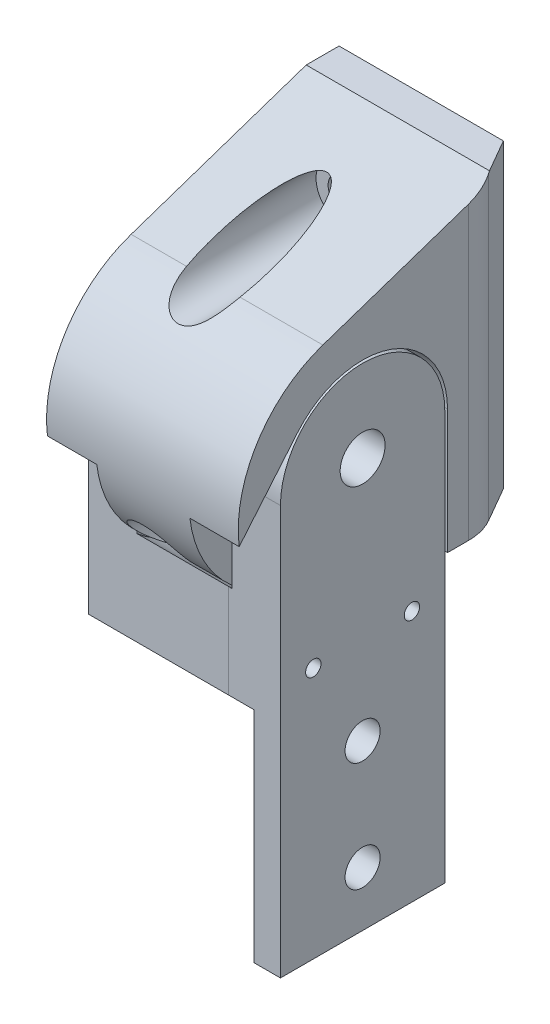
SolidWorks part; units mm, degrees
note: The reader was unsure of these and kept them because the rebuilt part matched: shared geometry of "Sketch1<3>", "Sketch1<5>", "Sketch1<8>", "Sketch1<9>", "Sketch1<11>", "Sketch2<4>", "Sketch2<5>", "Sketch3<3>", "Sketch7<3>", "Sketch7<5>".
ref_plane "Front Plane" through (0, 0, 0) normal (1, 0, 0) x (0, 1, 0)
ref_plane "Top Plane" through (0, 0, 0) normal (0, 0, 1) x (0, 1, 0)
ref_plane "Right Plane" through (0, 0, 0) normal (0, 1, 0) x (-1, 0, 0)
sketch "Sketch1" plane through (0, 0, 0) normal (1, 0, 0) x (0, 1, 0)
  line L0 (-22.7, 0) -> (-22.7, -30.7)
  line L1 (-74.7, 15) -> (-17.5379, 15)
  line L2 (-74.7, 15) -> (-74.7, -15)
  line L3 (-74.7, -15) -> (-17.5379, -15)
  line L4 (-17.5379, 15) -> (-17.5379, -15) construction
  line L5 (-22.7, -30.7) -> (32.3, -30.7)
  line L6 (21.5069, 7.2625) -> (32.3, -24.7)
  line L7 (32.3, -24.7) -> (32.3, -30.7)
  line L8 (-22.7, 0) -> (-17.5379, 0) construction
  line L9 (-74.7, 0) -> (-17.5379, 0) construction
  line L10 (-17.5379, 15) -> (0, 15)
  line L11 (0, -15) -> (-17.5379, -15)
  line L12 (-34.7, 15) -> (-34.7, -15)
  line L13 (-22.7, -15.5) -> (0, -15.5)
  line L14 (9.9632, 11.8737) -> (-2.7411, 22.5339)
  line L15 (-23.0776, 0) -> (-23.0776, -15)
  circle A0 centre (0, 0) radius 4.1
  circle A1 centre (0, 0) radius 7.7
  circle A2 centre (0, 0) radius 22.7
  arc A3 (0, 15) -> (0, -15) centre (0, 0) cw
  arc A4 (-17.5379, -15) -> (-17.5379, 15) centre (0, 0) cw
  circle A5 centre (-44.7, 0) radius 3.2
  circle A7 centre (-64.7, 0) radius 3.2
  arc A8 (0, -15.5) -> (9.9632, 11.8737) centre (0, 0) ccw
  point P5 (-17.0379, 15)
  point P7 (-67.9, 0)
  point P11 (-7.7, 0)
  point P15 (0, -22.7)
  dimension "D1" = 8.2
  dimension "D2" = 15.4
  dimension "D11" = 6.4
  dimension "D3" = 30
  dimension "D4" = 15
  dimension "D5" = 8
  dimension "D6" = 55
  dimension "D7" = 6
  dimension "D8" = 0.5
  dimension "D9" = 12
  dimension "D10" = 10
  dimension "D12" = 10
  dimension "D15" = 0.5
  dimension "D16" = 40
  dimension "D17" = 7.2
  dimension "D13" = 20
  dimension "D14" = 6.8
extrude "Boss-Extrude1" add sketch "Sketch1" along normal mid plane 17 contours L10 A2 L11 A1 | L13 A8 L14 A2 L10 A1 L11 | L3 A4 L0 | A4 L11 A2 L0 | A2 L11 L3 L0 L13
extrude "Boss-Extrude2" add sketch "Sketch1<3>" along normal mid plane 35 contours A2 L13 L0 L5 L7 L6 | A8 L13 A2 L14
sketch "Sketch1<3>" plane through (0, 0, 0) normal (1, 0, 0) x (0, 1, 0) same geometry as "Sketch1"
ref_plane "Plane1" through (8.7, 0, 0) normal (1, 0, 0) x (0, 0, -1)
extrude "Boss-Extrude3" add sketch "Sketch1<5>" along normal up to surface (8.8 mm away) from surface at 8.7 separate body contours A3 L10 A2 L11 A1 | A4 L0 A2 L10 | L3 A4 L0 | A4 L11 A2 L0 | L0 A4 L15 L3 | A1 A0 up to face at (17.5, 7.5284, -9.326) starting at plane "Plane1"
sketch "Sketch1<5>" plane through (0, 0, 0) normal (1, 0, 0) x (0, 1, 0) same geometry as "Sketch1"
ref_plane "Plane2" through (12.7, 0, 0) normal (-1, 0, 0) x (0, 0, 1)
extrude "Boss-Extrude5" add sketch "Sketch1<8>" along direction (1, 0, 0) on the side of the normal up to vertex (17.5 mm away) from surface at 12.7
sketch "Sketch1<8>" plane through (0, 0, 0) normal (1, 0, 0) x (0, 1, 0) same geometry as "Sketch1"
extrude "Boss-Extrude6" add sketch "Sketch1<9>" along normal up to surface (30.2 mm away) from vertex at -17.5 contours L15 A4 L1 L12 L3 up to face at (12.7, -64.7, 3.2) starting at point (-17.5, -22.7, -15.5)
sketch "Sketch1<9>" plane through (0, 0, 0) normal (1, 0, 0) x (0, 1, 0) same geometry as "Sketch1"
ref_plane "Plane3" through (-8.7, 0, 0) normal (-1, 0, 0) x (0, 0, 1)
extrude "Boss-Extrude7" add sketch "Sketch1<11>" against normal up to vertex from surface contours A3 L10 A2 L11 A1 | L3 A4 L0 | A4 L11 A2 L0 | L0 A4 L15 L3 | A4 L0 A2 L10 | A1 A0
sketch "Sketch1<11>" plane through (0, 0, 0) normal (1, 0, 0) x (0, 1, 0) same geometry as "Sketch1"
ref_plane "Plane4" through (8, 0, 0) normal (1, 0, 0) x (0, 1, 0)
split "Split1" trim tools "Plane4" bodies to split 109 resulting bodies 110 111
sketch "Sketch2" plane through (-17.5, 0, 0) normal (-1, 0, 0) x (0, -1, 0)
  line L4 (23.0776, 0) -> (23.0776, -15)
  line L5 (34.7, 15) -> (17.5379, 15)
  line L6 (34.7, -15) -> (34.7, 15)
  line L7 (23.0776, -15) -> (34.7, -15)
  line L8 (23.0776, 0) -> (23.0776, -15)
  line L9 (34.7, 15) -> (17.5379, 15)
  line L10 (34.7, -15) -> (34.7, 15)
  line L11 (23.0776, -15) -> (34.7, -15)
  circle A0 centre (28.7, -9) radius 1.7
  arc A1 (23.0776, 0) -> (17.5379, 15) centre (0, 0) ccw
  arc A2 (23.0776, 0) -> (17.5379, 15) centre (0, 0) ccw
  circle A3 centre (28.7, 9) radius 1.7
  circle A4 centre (28.7, 9) radius 3
  circle A5 centre (28.7, -9) radius 3
  circle A6 centre (28.7, 9) radius 1.4
  circle A7 centre (28.7, -9) radius 1.4
  dimension "D7" = 6
  dimension "D2" = 3.4
  dimension "D3" = 3.4
  dimension "D8" = 6
  dimension "D9" = 2.8
  dimension "D10" = 2.8
  dimension "D4" = 6
  dimension "D5" = 6
extrude "Cut-Extrude1" cut sketch "Sketch2" against normal through all contours A3 | A0 | A6 | A7
extrude "Cut-Extrude2" cut sketch "Sketch2<4>" against normal blind 4 contours A4 A3 | A5 A0
sketch "Sketch2<4>" plane through (-17.5, 0, 0) normal (-1, 0, 0) x (0, -1, 0) same geometry as "Sketch2"
extrude "Cut-Extrude3" cut sketch "Sketch2<5>" against normal through all contours A6 | A7
sketch "Sketch2<5>" plane through (-17.5, 0, 0) normal (-1, 0, 0) x (0, -1, 0) same geometry as "Sketch2"
sketch "Sketch3" plane through (0, -34.7, 0) normal (0, -1, 0) x (1, 0, 0)
  line L0 (-17.5, 0) -> (-2.5, 0) construction
  line L1 (-17.5, 15) -> (-17.5, -15) construction
  circle A0 centre (-2.5, 0) radius 3.2
  circle A1 centre (-2.5, 0) radius 6
  dimension "D1" = 6.4
  dimension "D2" = 12
  dimension "D3" = 15
extrude "Cut-Extrude4" cut sketch "Sketch3" against normal through all
extrude "Cut-Extrude5" cut sketch "Sketch3<3>" against normal through all from offset 5 offset against normal yes
sketch "Sketch3<3>" plane through (0, -34.7, 0) normal (0, -1, 0) x (1, 0, 0) same geometry as "Sketch3"
sketch "Sketch6" plane through (0, 32.3, 0) normal (0, 1, 0) x (-1, 0, 0)
  line L1 (-17.5, -15.5) -> (-17.5, -30.7) construction
  line L2 (-17.5, -15.5) -> (-17.5, -30.7)
  line L3 (-12.5, -30.7) -> (-16.1603, -24.3603)
  line L4 (17.5, -30.7) -> (17.5, -24.7)
  line L5 (17.5, -24.7) -> (-17.5, -24.7)
  line L6 (-17.5, -24.7) -> (-17.5, -30.7)
  line L7 (-17.5, -30.7) -> (17.5, -30.7)
  line L8 (17.5, -30.7) -> (17.5, -24.7)
  line L9 (17.5, -24.7) -> (-17.5, -24.7)
  line L10 (-17.5, -24.7) -> (-17.5, -30.7)
  line L11 (-17.5, -30.7) -> (17.5, -30.7)
  line L12 (-17.5, -30.7) -> (17.5, -30.7) construction
  arc A0 (-16.1603, -24.3603) -> (-17.5, -19.3603) centre (-7.5, -19.3603) cw
  point P2 (-12.5, -30.7)
  line M8 (17.5, -24.7) -> (-17.5, -24.7)
  line M9 (-17.5, -24.7) -> (-17.5, -30.7)
  line M10 (-17.5, -30.7) -> (17.5, -30.7)
  dimension "D4" = 10
  dimension "D2" = 30
  dimension "D3" = 60
  dimension "D1" = 0
extrude "Cut-Extrude6" cut sketch "Sketch6" against normal through all contours L3 M10 M8 M9 | L3 A0 L2 M8
sketch "Sketch7" plane through (0, 0, -30.7) normal (0, 0, -1) x (1, 0, 0)
  line L0 (8.5, -7.7) -> (8.5, 7.7) construction
  line L1 (-8.5, 7.7) -> (-8.5, -7.7) construction
  line L2 (8.5, -7.7) -> (8.5, 7.7)
  line L3 (-8.5, 7.7) -> (-8.5, -7.7)
  line L4 (-17.5, -32.3) -> (12.5, -32.3)
  line L5 (12.5, -32.3) -> (12.5, 22.7)
  line L6 (12.5, 22.7) -> (-17.5, 22.7)
  line L7 (-17.5, 22.7) -> (-17.5, -32.3)
  line L8 (-17.5, -32.3) -> (12.5, -32.3)
  line L9 (12.5, -32.3) -> (12.5, 22.7)
  line L10 (12.5, 22.7) -> (-17.5, 22.7)
  line L11 (-17.5, 22.7) -> (-17.5, -32.3)
  line L12 (-2.5, 22.7) -> (-2.5, -32.3) construction
  line L13 (-8.5, 7.7) -> (8.5, 7.7)
  line L14 (-8.5, -7.7) -> (8.5, -7.7)
  line L15 (12.5, -32.3) -> (-17.5, -32.3) construction
  circle A0 centre (-2.5, 15.7) radius 3
  circle A1 centre (-2.5, -23.3) radius 3
  circle A2 centre (-2.5, 15.7) radius 5.2
  circle A3 centre (-2.5, -23.3) radius 5.2
  dimension "D2" = 6
  dimension "D3" = 10.4
  dimension "D4" = 9
  dimension "D5" = 7
  dimension "D1" = 0
extrude "Cut-Extrude7" cut sketch "Sketch7" against normal through all contours A0 L12 | L12 A0 | L12 A1 | A1 L12
extrude "Cut-Extrude8" cut sketch "Sketch7<3>" against normal through all and the other way blind 1 from offset 15 contours A3 L12 A1 | L12 A3 A1 offset against normal yes
sketch "Sketch7<3>" plane through (0, 0, -30.7) normal (0, 0, -1) x (1, 0, 0) same geometry as "Sketch7"
extrude "Cut-Extrude12" cut sketch "Sketch7<5>" against normal through all from offset 33 contours A2 L12 A0 | L12 A2 A0
sketch "Sketch7<5>" plane through (0, 0, -30.7) normal (0, 0, -1) x (1, 0, 0) same geometry as "Sketch7"
equation "\"D15@Sketch1\"=\"D8@Sketch1\""
equation "\"D3@Sketch2\"=\"D2@Sketch2\""
equation "\"D10@Sketch2\"=\"D9@Sketch2\""
equation "\"D5@Sketch2\"=\"D4@Sketch2\""
